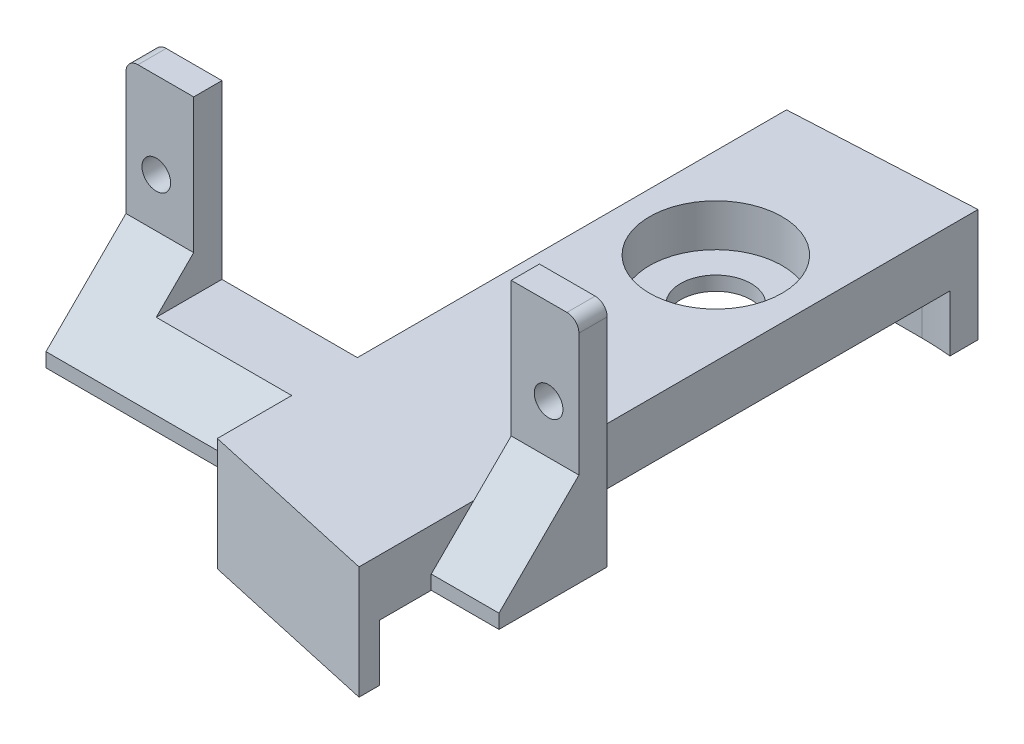
SolidWorks part; units mm, degrees
note: The reader was unsure of these and kept them because the rebuilt part matched: shared geometry of "Sketch2<3>".
ref_plane "Front Plane" through (0, 0, 0) normal (0, 0, 1) x (1, 0, 0)
ref_plane "Top Plane" through (0, 0, 0) normal (0, 1, 0) x (1, 0, 0)
ref_plane "Right Plane" through (0, 0, 0) normal (1, 0, 0) x (0, 0, -1)
sketch "Sketch1" plane through (0, 0, 0) normal (0, 0, 1) x (1, 0, 0)
  line L0 (11.25, -6.1) -> (15.2, -6.1)
  line L1 (11.25, -6.1) -> (11.25, 6.0941)
  line L2 (11.25, 6.0941) -> (15.2, 6.1)
  line L3 (15.2, -6.1) -> (-15.2, -6.1) construction
  line L4 (-10.5, 6.1) -> (-15.2, 6.1) construction
  line L5 (-16.05, 5.25) -> (-16.05, -5.25) construction
  line L6 (-16.05, -5.25) -> (-16.05, -0.55) construction
  line L9 (15.2, -6.1) -> (11.25, -6.1)
  line L10 (-11.25, 6.1) -> (-15.2, 6.1)
  line L11 (-16.05, 5.25) -> (-16.05, -5.25)
  line L12 (-16.05, -5.25) -> (-16.05, -0.55)
  line L13 (16.05, 5.25) -> (16.05, -5.25)
  line L14 (-15.2, -6.1) -> (-16.05, -6.1)
  line L15 (-11.25, 6.1) -> (-11.25, -6.1)
  line L16 (-11.25, -5.25) -> (-11.25, 5.25) construction
  line L17 (-11.25, -5.25) -> (-11.25, 5.25) construction
  line L18 (-15.2, 6.1) -> (15.2, 6.1) construction
  line L19 (-11.25, -6.1) -> (-15.2, -6.1)
  line L20 (-16.05, -5.25) -> (-16.05, -6.1)
  line L21 (15.2, -6.1) -> (16.05, -6.1)
  line L22 (16.05, -5.25) -> (16.05, -6.1)
  arc A0 (-15.2, 6.1) -> (-16.05, 5.25) centre (-15.2, 5.25) ccw construction
  arc A1 (-16.05, -5.25) -> (-15.2, -6.1) centre (-15.2, -5.25) ccw construction
  arc A2 (15.2, -6.1) -> (16.05, -5.25) centre (15.2, -5.25) ccw construction
  arc A3 (16.05, 5.25) -> (15.2, 6.1) centre (15.2, 5.25) ccw construction
  arc A4 (-15.2, 6.1) -> (-16.05, 5.25) centre (-15.2, 5.25) ccw
  arc A5 (-16.05, -5.25) -> (-15.2, -6.1) centre (-15.2, -5.25) ccw
  arc A6 (15.2, -6.1) -> (16.05, -5.25) centre (15.2, -5.25) ccw
  arc A7 (16.05, 5.25) -> (15.2, 6.1) centre (15.2, 5.25) ccw
  circle A8 centre (-13.9, 0) radius 1.016
  circle A9 centre (13.9, 0) radius 1.016
  dimension "D1" = 2.032
  dimension "D2" = 2.032
extrude "Boss-Extrude1" add sketch "Sketch1" along normal blind 2 contours L11 A5 L19 L15 L10 A4 A8 | L13 A7 L2 L1 L0 A6 A9 | A6 L21 L22 | A5 L20 L14
sketch "Sketch2" plane through (0, -6.1, 0) normal (0, -1, 0) x (1, 0, 0)
  line L0 (-16.05, 2) -> (16.05, 2)
  line L5 (16.05, 2) -> (16.05, 0)
  line L6 (16.05, 0) -> (-16.05, 0)
  line L7 (-16.05, 0) -> (-16.05, 2)
  line L8 (-1.65, 9.9254) -> (-1.65, -30.4103)
  line L9 (11.25, 2) -> (11.25, 12.7845)
  line L10 (-1.65, -30.4103) -> (11.25, -31.0792)
  line L11 (9.15, -29.2) -> (4.75, -29.2)
  line L12 (2.3246, 8.8937) -> (37.1754, 17.6063) construction
  line L18 (2.3246, 8.8937) -> (11.25, 11.125)
  line L19 (11.25, 0) -> (11.25, -31.0792)
  line L22 (2.2761, 9.0877) -> (11.2015, 11.319)
  line L24 (9.15, -29) -> (4.75, -29)
  line L26 (11.2015, 11.319) -> (11.25, 11.3375)
  line L30 (-1.65, 9.9254) -> (11.25, 12.7845)
  circle A1 centre (4.75, -19) radius 4.7
  arc A4 (2.3246, 8.8937) -> (-5.25, -0.8078) centre (4.75, -0.8078) ccw construction
  arc A5 (9.15, -29) -> (11.25, -28.8894) centre (9.15, -9) ccw
  arc A10 (-1.65, -26.6837) -> (4.75, -29) centre (4.75, -19) ccw
  arc A11 (-1.65, -26.9423) -> (4.75, -29.2) centre (4.75, -19) ccw
  arc A12 (2.3246, 8.8937) -> (-1.65, 6.876) centre (4.75, -0.8078) ccw
  arc A13 (9.15, -29.2) -> (11.25, -29.0905) centre (9.15, -9) ccw
  arc A14 (2.2761, 9.0877) -> (-1.65, 7.1345) centre (4.75, -0.8078) ccw
  arc A16 (2.2761, 9.0877) -> (-1.778, 7.0297) centre (4.75, -0.8078) ccw construction
  arc A17 (-1.778, -26.8374) -> (4.75, -29.2) centre (4.75, -19) ccw construction
  arc A18 (9.15, -29.2) -> (11.271, -29.0883) centre (9.15, -9) ccw construction
  point P28 (-6.5991, -18.7771)
  point P29 (-19.7755, -35.4742)
  point P30 (3.3836, -37.5589)
  point P31 (14.7015, -31.0792)
  point P32 (3.6798, -24.3792)
  point P33 (-7.2167, -27.2566)
  point P37 (4.75, -19)
  point P38 (4.75, -29.2)
  point P39 (12.8214, 0)
  point P40 (11.38, -26.7513)
  point P43 (12.8214, 6.5789)
  point P44 (-80.0361, -11.1071)
  point P45 (-172.8435, 6.8395)
  point P46 (-2.7186, 49.3707)
  point P47 (-2.7186, 0)
  point P50 (8.5784, 18.1443)
  point P51 (5.1008, 9.2671)
  point P52 (11.3818, 16.4399)
  point P54 (-1.65, 16.9869)
  point P55 (-1.65, 9.9254)
  point P56 (-1.65, -31.5862)
  point P58 (-1.65, -30.4103)
  point P59 (11.25, -31.0792)
  dimension "D3" = 6.4
  dimension "D6" = 9.4
  dimension "D1" = 11.3
  dimension "D2" = 19
  dimension "D4" = 6.5
  dimension "D5" = 0.2
extrude "Boss-Extrude2" add sketch "Sketch2" along normal blind 3
extrude "Boss-Extrude5" add sketch "Sketch2<3>" along normal blind 8
sketch "Sketch2<3>" plane through (0, -6.1, 0) normal (0, -1, 0) x (1, 0, 0) same geometry as "Sketch2"
sketch "Sketch3" plane through (11.25, 0, 0) normal (1, 0, 0) x (0, 0, -1)
  line L0 (-7.6658, -9.1) -> (-2, -3.4575)
  line L1 (-2, -9.1) -> (-11.3375, -9.1) construction
  line L2 (-2, -9.1) -> (-2, 5.25) construction
  line L3 (-2, -3.4575) -> (-2, -9.1)
  line L4 (-2, -9.1) -> (-7.6658, -9.1)
  line L5 (-2, -6.1) -> (-2, 6.0941) construction
extrude "Boss-Extrude6" add sketch "Sketch3" along normal up to surface and the other way up to surface up to face at (16.05, -1.925, 1) other way up to face at (-16.05, -1.925, 1)
sketch "Sketch4" plane through (0, -6.1, 0) normal (0, 1, 0) x (1, 0, 0)
  line L0 (-11.25, 0) -> (-11.25, -14.1277)
  line L1 (-11.25, -14.1277) -> (11.25, -14.1277)
  line L2 (11.25, -4.6534) -> (11.25, -12.7845) construction
  line L3 (11.25, -14.1277) -> (11.25, 0)
  line L4 (11.25, 0) -> (-11.25, 0)
extrude "Cut-Extrude1" cut sketch "Sketch4" along normal blind 7
sketch "Sketch5" plane through (0, -9.1, 0) normal (0, -1, 0) x (1, 0, 0)
  line L3 (16.05, 7.6658) -> (11.25, 7.6658)
  line L12 (-1.65, 0) -> (-1.65, -26.9423)
  line L14 (-1.65, 0) -> (-1.65, -26.9423)
  line L16 (-16.05, 0) -> (-1.65, 0)
  line L19 (-16.05, 7.6658) -> (-16.05, 0)
  line L20 (-16.05, 7.6658) -> (-16.05, 0)
  line L21 (16.05, 0) -> (16.05, 7.6658)
  line L29 (-16.05, 0) -> (-1.65, 0)
  line L34 (16.05, 0) -> (16.05, 7.6658)
  line L41 (11.25, 0) -> (16.05, 0)
  line L42 (11.25, 0) -> (16.05, 0)
  line L43 (11.25, 11.3375) -> (11.2015, 11.319)
  line L45 (11.25, 7.6658) -> (11.25, 11.3375)
  line L46 (11.25, 7.6658) -> (11.25, 11.3375)
  line L52 (11.25, -29.0905) -> (11.25, 0)
  line L55 (11.25, -29.0905) -> (11.25, 0)
  line L57 (11.25, 11.3375) -> (11.2015, 11.319)
  line L59 (11.2015, 11.319) -> (2.2761, 9.0877)
  line L62 (11.2015, 11.319) -> (2.2761, 9.0877)
  line L65 (16.05, 7.6658) -> (11.25, 7.6658)
  line L67 (4.75, -29.2) -> (9.15, -29.2)
  line L68 (4.75, -29.2) -> (9.15, -29.2)
  line L70 (-1.65, 7.1345) -> (-1.65, 7.6658)
  line L72 (-1.65, 7.1345) -> (-1.65, 7.6658)
  line L73 (-1.65, 7.6658) -> (-16.05, 7.6658)
  line L74 (-1.65, 7.6658) -> (-16.05, 7.6658)
  circle A0 centre (4.75, -19) radius 2.5
  arc A5 (2.2761, 9.0877) -> (-1.65, 7.1345) centre (4.75, -0.8078) ccw
  arc A15 (2.2761, 9.0877) -> (-1.65, 7.1345) centre (4.75, -0.8078) ccw
  arc A18 (-1.65, -26.9423) -> (4.75, -29.2) centre (4.75, -19) ccw
  arc A20 (-1.65, -26.9423) -> (4.75, -29.2) centre (4.75, -19) ccw
  arc A21 (9.15, -29.2) -> (11.25, -29.0905) centre (9.15, -9) ccw
  arc A22 (9.15, -29.2) -> (11.25, -29.0905) centre (9.15, -9) ccw
  dimension "D1" = 5
  dimension "D2" = 0
extrude "Boss-Extrude7" add sketch "Sketch5" along normal blind 1
